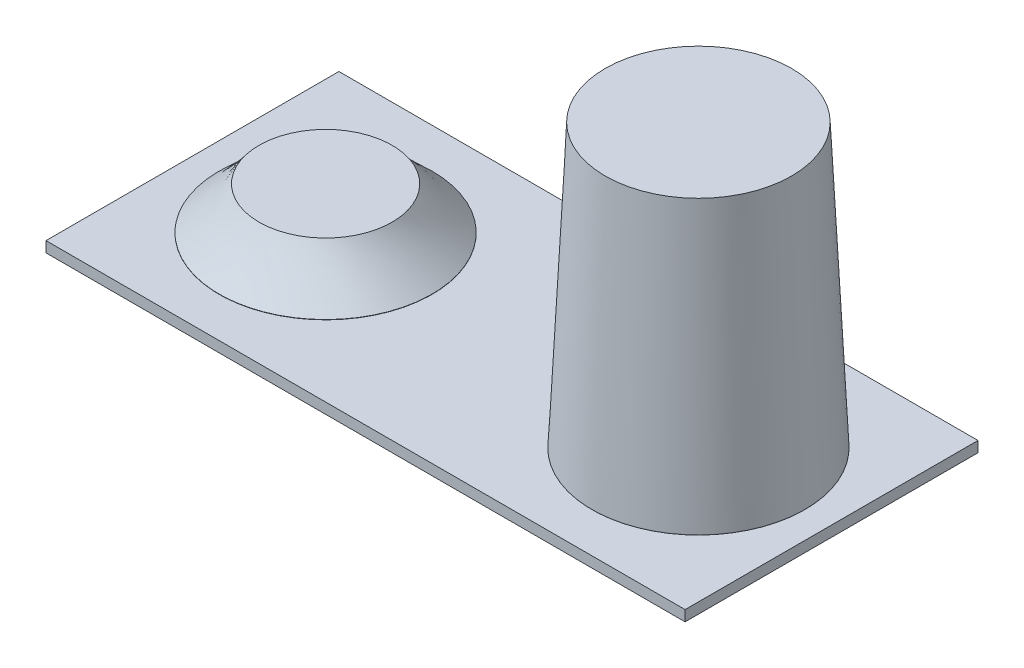
SolidWorks part; units mm, degrees
ref_plane "前视基准面" through (0, 0, 0) normal (0, 0, 1) x (1, 0, 0)
ref_plane "上视基准面" through (0, 0, 0) normal (0, 1, 0) x (1, 0, 0)
ref_plane "右视基准面" through (0, 0, 0) normal (1, 0, 0) x (0, 0, -1)
other "Configuration Table"
sketch "草图1" plane through (0, 0, 0) normal (0, 1, 0) x (1, 0, 0)
  line L1 (-5, -5) -> (5, -5)
  line L2 (-5, -5) -> (-5, 5)
  line L3 (-5, 5) -> (5, 5)
  line L4 (5, -5) -> (5, 5)
  line L5 (-5, -5) -> (5, 5) construction
  line L6 (-5, 5) -> (5, -5) construction
  line L15 (9, -5) -> (19, -5)
  line L16 (9, -5) -> (9, 5)
  line L17 (9, 5) -> (19, 5)
  line L18 (19, -5) -> (19, 5)
  line L19 (9, -5) -> (19, 5) construction
  line L20 (9, 5) -> (19, -5) construction
  line L21 (5, 5) -> (9, 5)
  line L22 (5, 5) -> (5, -5)
  line L23 (5, -5) -> (9, -5)
  line L24 (9, 5) -> (9, -5)
  line L25 (-5, 5.5) -> (19, 5.5)
  line L26 (-5, 5.5) -> (-5, -5.5)
  line L27 (-5, -5.5) -> (19, -5.5)
  line L28 (19, 5.5) -> (19, -5.5)
  circle A0 centre (0, 0) radius 4
  circle A1 centre (0, 0) radius 2.5
  circle A2 centre (14, 0) radius 4
  circle A3 centre (14, 0) radius 3.5
  point P9 (14, 0)
  point P20 (0, 0)
  point P21 (19, 0)
  dimension "D1" = 8
  dimension "D2" = 5
  dimension "D7" = 14
  dimension "D5" = 7
  dimension "D6" = 8
  dimension "D3" = 10
  dimension "D4" = 24
  dimension "D8" = 11
extrude "凸台-拉伸1" add sketch "草图1" along normal blind 0.4 contours L25 L28 L27 L26
extrude "凸台-拉伸2" add sketch "草图1<5>" along normal blind 1.6 from surface contours A1 starting at face at (7, 0.4, 0)
sketch "草图1<5>" plane through (0, 0, 0) normal (0, 1, 0) x (1, 0, 0) same geometry as "草图1"
extrude "凸台-拉伸3" add sketch "草图1<6>" along normal blind 0.01 from surface contours A0 | A2 starting at face at (0, 0.4, 2.5)
sketch "草图1<6>" plane through (0, 0, 0) normal (0, 1, 0) x (1, 0, 0) same geometry as "草图1"
loft "放样1" add section edge at (0, 2, 2.5) section edge at (0, 0.41, 4) connector at (-2.2492, 2, 1.0914) connector at (-2.4237, 0.41, 3.1821)
extrude "凸台-拉伸4" add sketch "草图1<7>" along normal blind 10.6 from surface contours A3 starting at face at (14, 0.4, 4)
sketch "草图1<7>" plane through (0, 0, 0) normal (0, 1, 0) x (1, 0, 0) same geometry as "草图1"
loft "放样2" add section edge at (14, 11, 3.5) section edge at (14, 0.41, 4) connector at (12.0182, 11, 2.8849) connector at (11.825, 0.41, 3.357)
